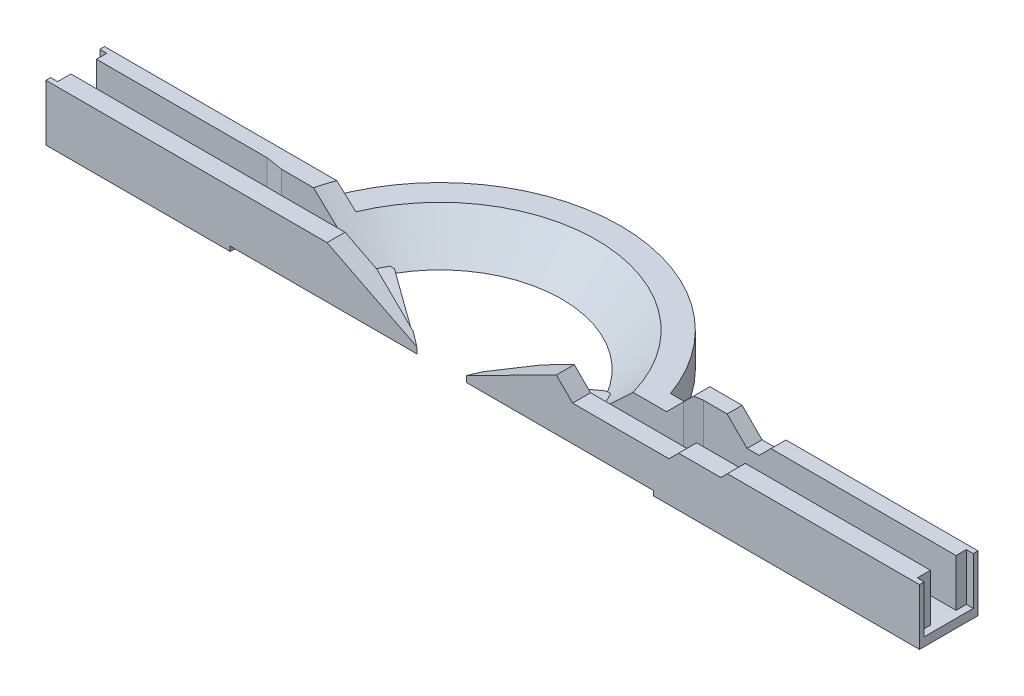
SolidWorks part; units mm, degrees
ref_plane "Front Plane" through (0, 0, 0) normal (0, 0, 1) x (1, 0, 0)
ref_plane "Top Plane" through (0, 0, 0) normal (0, 1, 0) x (1, 0, 0)
ref_plane "Right Plane" through (0, 0, 0) normal (1, 0, 0) x (0, 0, -1)
ref_plane "Plane4" through (0, 88.9762, 0) normal (0, 1, 0) x (1, 0, 0)
ref_plane "Plane1" through (0, 0, -145.923) normal (0, 0, 1) x (1, 0, 0)
ref_plane "Plane2" through (330.2, 0, 0) normal (1, 0, 0) x (0, 0, -1)
ref_plane "Plane3" through (300.0502, 0, 0) normal (1, 0, 0) x (0, 0, -1)
sketch "Sketch5" plane through (0, 88.9762, 0) normal (0, 1, 0) x (1, 0, 0)
  line L0 (281.7495, 153.8224) -> (9.144, 153.8224)
  line L1 (9.144, 153.8224) -> (9.144, 157.3022)
  line L2 (9.144, 196.85) -> (230.4767, 196.85)
  line L4 (281.7495, 153.8224) -> (261.3232, 167.0304)
  line L7 (14.224, 167.0304) -> (261.3232, 167.0304)
  line L8 (152.4, 183.7944) -> (235.3976, 183.7944)
  line L9 (152.4, 183.7944) -> (139.7, 185.8264)
  line L10 (139.7, 185.8264) -> (14.224, 185.8264)
  line L11 (300.0375, 152.4) -> (300.0375, 387.3754) construction
  line L12 (9.144, 193.3702) -> (14.224, 193.3702)
  line L13 (14.224, 193.3702) -> (14.224, 185.8264)
  line L14 (14.224, 157.3022) -> (9.144, 157.3022)
  line L15 (9.144, 193.3702) -> (9.144, 196.85)
  line L16 (14.224, 167.0304) -> (14.224, 157.3022)
  line L17 (235.3976, 183.7944) -> (226.3629, 189.6364)
  line L18 (364.6774, 183.7944) -> (373.7121, 189.6364)
  line L20 (460.375, 185.8264) -> (646.176, 185.8264)
  line L21 (447.675, 183.7944) -> (460.375, 185.8264)
  line L22 (447.675, 183.7944) -> (364.6774, 183.7944)
  line L23 (646.176, 167.0304) -> (338.7518, 167.0304)
  line L24 (318.3255, 153.8224) -> (338.7518, 167.0304)
  line L25 (651.256, 196.85) -> (369.5983, 196.85)
  line L26 (318.3255, 153.8224) -> (651.256, 153.8224)
  line L29 (651.256, 193.3702) -> (651.256, 196.85)
  line L30 (651.256, 153.8224) -> (651.256, 157.3022)
  line L31 (646.176, 157.3022) -> (651.256, 157.3022)
  line L32 (646.176, 167.0304) -> (646.176, 157.3022)
  line L33 (646.176, 193.3702) -> (646.176, 185.8264)
  line L34 (651.256, 193.3702) -> (646.176, 193.3702)
  arc A1 (230.4767, 196.85) -> (226.3629, 189.6364) centre (300.0375, 152.4) ccw
  arc A2 (369.5983, 196.85) -> (373.7121, 189.6364) centre (300.0375, 152.4) cw
  point P2 (9.144, 155.5623)
  point P3 (651.256, 155.5623)
  point P10 (9.144, 195.1101)
  dimension "D17" = 82.55
  dimension "D1" = 153.8224
  dimension "D2" = 13.208
  dimension "D3" = 18.796
  dimension "D4" = 16.764
  dimension "D5" = 43.0276
  dimension "D6" = 300.0375
  dimension "D7" = 290.8935
  dimension "D8" = 36.068
  dimension "D9" = 642.112
  dimension "D10" = 5.08
  dimension "D11" = 5.08
  dimension "D12" = 130.556
  dimension "D13" = 143.256
  dimension "D14" = 73.6746
  dimension "D15" = 18.288
  dimension "D16" = 57.113
extrude "Boss-Extrude4" add sketch "Sketch5" along normal blind 41.275
sketch "Sketch22" plane through (0, 0, -153.8224) normal (0, 0, 1) x (1, 0, 0)
  line L0 (318.3255, 96.9263) -> (384.3166, 130.2512)
  line L1 (318.3255, 130.2512) -> (651.256, 130.2512) construction
  line L2 (384.3166, 130.2512) -> (215.7584, 130.2512)
  line L3 (9.144, 130.2512) -> (281.7495, 130.2512) construction
  line L4 (215.7584, 130.2512) -> (281.7495, 96.9263)
  line L6 (23.6652, 0) -> (-23.6652, 0) construction
  line L8 (300.0375, 197.4678) -> (300.0375, -129.8287) construction
  line L15 (281.7495, 96.9263) -> (281.7495, 92.1512)
  line L16 (281.7495, 92.1512) -> (318.3255, 92.1512)
  line L19 (318.3255, 92.1512) -> (318.3255, 96.9263)
  dimension "D1" = 168.5583
  dimension "D2" = 4.7751
  dimension "D3" = 92.1512
  dimension "D4" = 215.7584
  dimension "D5" = 281.7495
extrude "Cut-Extrude12" cut sketch "Sketch22<2>" against normal offset from surface (10.668 mm away) 2.54 up to face at (137.7736, 109.6137, -167.0304)
sketch "Sketch22<2>" plane through (0, 0, -153.8224) normal (0, 0, 1) x (1, 0, 0) same geometry as "Sketch22"
extrude "Cut-Extrude13" cut sketch "Sketch22<3>" against normal up to surface (29.972 mm away) up to face at (193.8988, 109.6137, -183.7944)
sketch "Sketch22<3>" plane through (0, 0, -153.8224) normal (0, 0, 1) x (1, 0, 0) same geometry as "Sketch22"
extrude "Cut-Extrude7" cut sketch "Sketch22" against normal through all
sketch "Sketch26" plane through (0, 0, -153.8224) normal (0, 0, 1) x (1, 0, 0)
  line L0 (510.032, 130.2512) -> (505.206, 125.4252)
  line L1 (384.3166, 130.2512) -> (651.256, 130.2512) construction
  line L2 (505.206, 125.4252) -> (474.218, 125.4252)
  line L3 (474.218, 125.4252) -> (467.106, 118.3132)
  line L4 (467.106, 118.3132) -> (396.2546, 118.3132)
  line L5 (396.2546, 118.3132) -> (384.3166, 130.2512)
  line L6 (651.256, 130.2512) -> (651.256, 88.9762) construction
  line L7 (23.6652, 0) -> (-23.6652, 0) construction
  line L9 (308.8696, -20.6465) -> (308.8696, 110.4851) construction
  line L13 (384.3166, 130.2512) -> (510.032, 130.2512)
  dimension "D1" = 125.4252
  dimension "D2" = 146.05
  dimension "D3" = 135
  dimension "D4" = 184.15
  dimension "D6" = 118.3132
  dimension "D7" = 135
  dimension "D8" = 135
  dimension "D9" = 342.3864
extrude "Cut-Extrude9" cut sketch "Sketch26" against normal blind 15.24
sketch "Sketch42" plane through (0, 130.2512, 0) normal (0, 1, 0) x (1, 0, 0)
  line L0 (651.256, 196.85) -> (384.3166, 196.85) construction
  line L1 (396.2546, 196.85) -> (510.032, 196.85)
  line L2 (396.2546, 196.85) -> (396.2546, 183.7944)
  line L4 (510.032, 196.85) -> (510.032, 185.8264)
  line L5 (510.032, 167.0304) -> (510.032, 153.8224) construction
  line L6 (396.2546, 167.0304) -> (396.2546, 153.8224) construction
  line L7 (460.375, 185.8264) -> (646.176, 185.8264) construction
  line L8 (447.675, 183.7944) -> (460.375, 185.8264) construction
  line L9 (384.3166, 183.7944) -> (447.675, 183.7944) construction
  line L10 (460.375, 185.8264) -> (510.032, 185.8264)
  line L11 (447.675, 183.7944) -> (460.375, 185.8264)
  line L12 (396.2546, 183.7944) -> (447.675, 183.7944)
  point P15 (396.2546, 160.4264)
extrude "Boss-Extrude6" add sketch "Sketch42" along normal blind 5.969
sketch "Sketch36" plane through (0, 0, -196.85) normal (0, 0, 1) x (1, 0, 0)
  line L1 (505.206, 125.4252) -> (510.032, 130.2512) construction
  line L2 (435.356, 117.4242) -> (454.2028, 136.271)
  line L5 (492.506, 121.5849) -> (501.3657, 121.5849)
  line L6 (501.3657, 121.5849) -> (510.032, 130.2512)
  line L7 (510.032, 130.2512) -> (646.176, 130.2512) construction
  line L9 (332.4807, 151.7667) -> (332.4807, 117.4242)
  line L10 (72.2808, 0) -> (-72.2808, 0) construction
  line L11 (651.256, 130.2512) -> (651.256, 88.9762) construction
  line L13 (435.356, 117.4242) -> (332.4807, 117.4242)
  line L14 (477.8199, 136.271) -> (454.2028, 136.271)
  line L15 (492.506, 121.5849) -> (477.8199, 136.271)
  line L16 (510.032, 130.2512) -> (651.256, 130.2512) construction
  line L17 (510.032, 130.2512) -> (531.5475, 151.7667)
  line L18 (531.5475, 151.7667) -> (332.4807, 151.7667)
  line L19 (384.3166, 130.2512) -> (396.2546, 130.2512) construction
  dimension "D1" = 12.827
  dimension "D2" = 121.5849
  dimension "D3" = 158.75
  dimension "D4" = 6.0198
  dimension "D5" = 215.9
  dimension "D6" = 135
  dimension "D7" = 135
extrude "Cut-Extrude15" cut sketch "Sketch36" along normal blind 19.05
sketch "Sketch37" plane through (300.0502, 0, 0) normal (1, 0, 0) x (0, 0, -1)
  line L0 (238.506, 88.9762) -> (285.242, 88.9762)
  line L1 (285.242, 88.9762) -> (285.242, 117.4242)
  line L3 (267.462, 117.4242) -> (238.506, 88.9762)
  line L4 (285.242, 117.4242) -> (267.462, 117.4242)
  line L5 (153.8224, 130.2512) -> (153.8224, 88.9762) construction
  line L6 (157.3022, 88.9762) -> (167.0304, 88.9762) construction
  line L7 (152.4, 133.0917) -> (152.4, 75.4728) construction
  point P9 (162.1663, 88.9762)
  dimension "D1" = 46.736
  dimension "D2" = 28.448
  dimension "D3" = 17.78
  dimension "D4" = 131.4196
  dimension "D5" = 1.4224
revolve "Revolve1" add sketch "Sketch37" angle 142 mid plane about L7
sketch "Sketch41" plane through (300.0502, 0, 0) normal (1, 0, 0) x (0, 0, -1)
  line L0 (290.2131, 139.7762) -> (238.506, 88.9762)
  line L1 (238.506, 88.9762) -> (267.462, 117.4242) construction
  line L2 (152.4, 150.9734) -> (152.4, 66.1289) construction
  line L3 (153.8224, 130.2512) -> (153.8224, 88.9762) construction
  line L4 (171.45, 139.7762) -> (171.45, 88.9762)
  line L5 (171.45, 139.7762) -> (290.2131, 139.7762)
  line L6 (171.45, 88.9762) -> (238.506, 88.9762)
  line L7 (196.85, 88.9762) -> (238.506, 88.9762) construction
  dimension "D1" = 1.4224
  dimension "D2" = 19.05
  dimension "D3" = 50.8
revolve "Cut-Revolve1" cut sketch "Sketch41" angle 153 mid plane about L2
sketch "Sketch39" plane through (0, 88.9762, 0) normal (0, -1, 0) x (1, 0, 0)
  line L1 (9.144, -153.8224) -> (651.256, -153.8224)
  line L2 (9.144, -153.8224) -> (9.144, -196.85)
  line L3 (9.144, -196.85) -> (651.256, -196.85)
  line L4 (651.256, -153.8224) -> (651.256, -196.85)
  line L5 (9.144, -153.8224) -> (651.256, -196.85) construction
  line L6 (9.144, -196.85) -> (651.256, -153.8224) construction
  line L7 (9.144, -157.3022) -> (9.144, -153.8224) construction
  line L8 (9.144, -153.8224) -> (281.7495, -153.8224) construction
  line L9 (174.8656, -196.85) -> (9.144, -196.85) construction
  line L10 (651.256, -153.8224) -> (651.256, -157.3022) construction
  point P4 (330.2, -175.3362)
  point P9 (9.144, -155.5623)
extrude "Boss-Extrude5" add sketch "Sketch39" against normal blind 6.35
sketch "Sketch38" plane through (0, 88.9762, 0) normal (0, -1, 0) x (1, 0, 0)
  circle A0 centre (300.0502, -152.4) radius 155.575
  dimension "D1" = 311.15
extrude "Cut-Extrude14" cut sketch "Sketch38" against normal blind 3.429
sketch "Sketch43" plane through (0, 136.2202, 0) normal (0, 1, 0) x (1, 0, 0)
  line L0 (281.7495, 153.8224) -> (222.2576, 196.85)
  line L2 (318.3255, 153.8224) -> (377.8428, 196.85)
  line L3 (281.7495, 153.8224) -> (318.3255, 153.8224)
  arc A0 (377.8428, 196.85) -> (222.2576, 196.85) centre (300.0502, 152.4) ccw construction
  arc A1 (377.8428, 196.85) -> (222.2576, 196.85) centre (300.0502, 152.4) ccw
extrude "Cut-Extrude16" cut sketch "Sketch43" against normal through all
